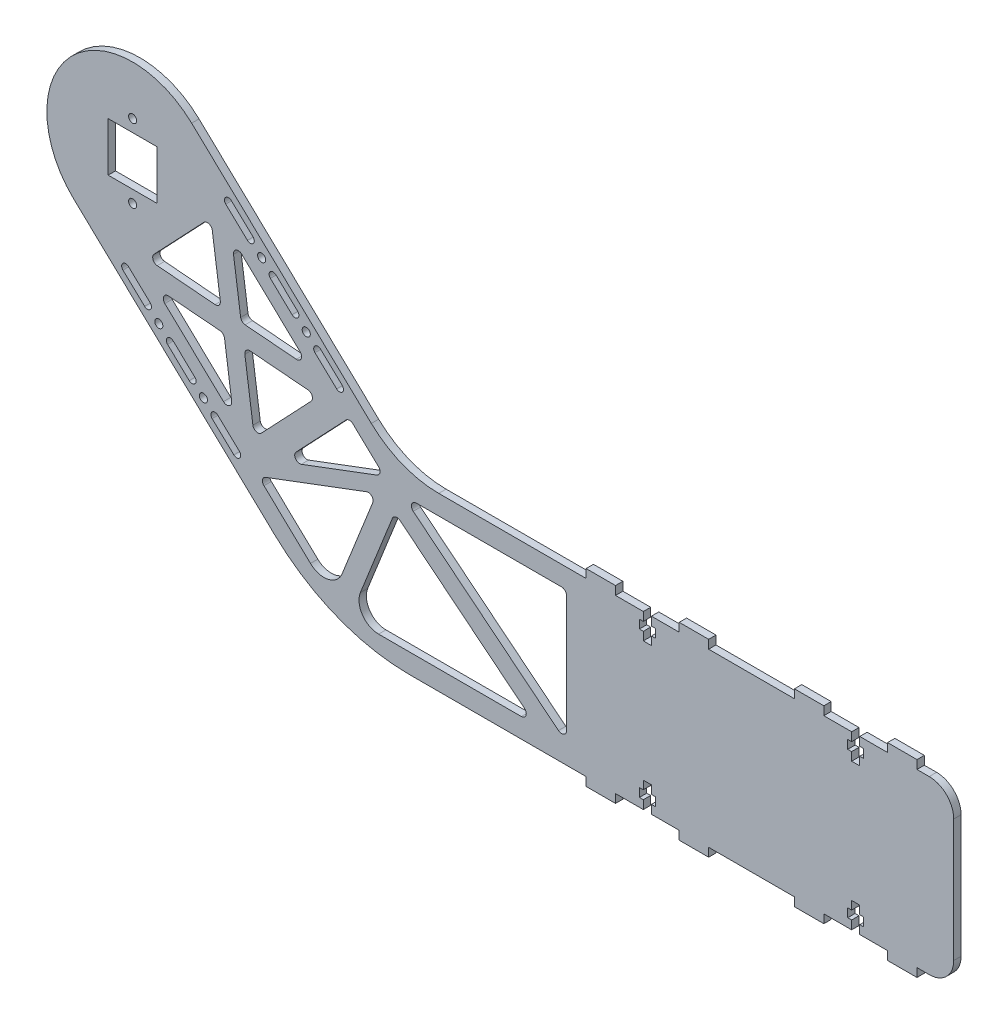
SolidWorks part; units mm, degrees
material "Thornel Mat VMA"
ref_plane "前视基准面" through (0, 0, 0) normal (0, 0, 1) x (1, 0, 0)
ref_plane "上视基准面" through (0, 0, 0) normal (0, 1, 0) x (1, 0, 0)
ref_plane "右视基准面" through (0, 0, 0) normal (1, 0, 0) x (0, 0, -1)
sketch "草图1" plane through (0, 0, 0) normal (0, 0, 1) x (1, 0, 0)
  line L0 (0, 0) -> (95, -90) construction
  line L1 (95, -90) -> (335, -90) construction
  line L2 (-24.0711, -25.4083) -> (81.0535, -125)
  line L3 (81.0535, -125) -> (335, -125)
  line L4 (24.0711, 25.4083) -> (108.9465, -55)
  line L5 (108.9465, -55) -> (335, -55)
  line L6 (335, -55) -> (335, -125)
  circle A1 centre (0, 0) radius 7.65
  circle A2 centre (0, 0) radius 35
  dimension "D6" = 15.3
  dimension "D1" = 240
  dimension "D2" = 335
  dimension "D3" = 90
  dimension "D4" = 35
  dimension "D5" = 35
extrude "凸台-拉伸1" add sketch "草图1" along normal blind 3 contours L2 L3 L6 L5 L4 A1 | A2 A1 region at (167.1612, -80.12, 0) region at (-24.6897, 23.3902, 0)
sketch "草图3" plane through (0, 0, 3) normal (0, 0, 1) x (1, 0, 0)
  line L0 (210, -55) -> (210, -125) construction
  line L1 (293.35, -55) -> (293.35, -58.5)
  line L2 (108.9465, -55) -> (335, -55) construction
  line L3 (293.35, -58.5) -> (291.75, -58.5)
  line L4 (291.75, -58.5) -> (291.75, -62)
  line L5 (81.0535, -125) -> (335, -125) construction
  line L8 (335, -90) -> (97.2271, -90) construction
  line L9 (335, -55) -> (335, -125) construction
  line L12 (39.125, 4.9479) -> (47.9817, -3.4425) construction
  line L13 (40.2598, 6.1458) -> (49.1164, -2.2447)
  line L14 (37.9903, 3.7501) -> (46.8469, -4.6404)
  line L15 (-2.7794, -39.2843) -> (102.3452, -138.876) construction
  line L16 (15.3695, -56.4779) -> (24.2261, -64.8684) construction
  line L17 (16.5042, -55.2801) -> (25.3609, -63.6706)
  line L18 (-20.9762, -22.1416) -> (84.1483, -121.7332)
  line L19 (-20.9762, -22.1416) -> (84.1483, -121.7332) construction
  line L20 (208.35, -55) -> (208.35, -58.5)
  line L21 (20.9762, 22.1416) -> (105.8517, -58.2668)
  line L22 (20.9762, 22.1416) -> (105.8517, -58.2668) construction
  line L25 (208.35, -58.5) -> (206.75, -58.5)
  line L28 (206.75, -58.5) -> (206.75, -62)
  line L31 (206.75, -62) -> (208.35, -62)
  line L34 (14.2347, -57.6758) -> (23.0913, -66.0662)
  line L37 (-2.8274, -39.3352) -> (6.0292, -47.7257) construction
  line L38 (-1.6926, -38.1374) -> (7.164, -46.5278)
  line L39 (-3.9622, -40.533) -> (4.8944, -48.9235)
  line L40 (57.3219, -12.1948) -> (66.1785, -20.5853) construction
  line L41 (58.4567, -10.997) -> (67.3133, -19.3875)
  line L42 (56.1871, -13.3926) -> (65.0437, -21.7831)
  line L43 (15.4175, -56.4271) -> (120.542, -156.0187) construction
  line L44 (33.5663, -73.6207) -> (42.4229, -82.0112) construction
  line L45 (34.7011, -72.4229) -> (43.5577, -80.8134)
  line L46 (32.4315, -74.8185) -> (41.2882, -83.209)
  line L47 (75.5187, -29.3376) -> (84.3754, -37.7281) construction
  line L48 (76.6535, -28.1398) -> (85.5101, -36.5303)
  line L49 (74.384, -30.5354) -> (83.2406, -38.9259)
  line L50 (208.35, -62) -> (208.35, -65.4)
  line L51 (208.35, -65.4) -> (211.65, -65.4)
  line L52 (211.65, -65.4) -> (211.65, -62)
  line L53 (211.65, -62) -> (213.25, -62)
  line L54 (213.25, -62) -> (213.25, -58.5)
  line L55 (213.25, -58.5) -> (211.65, -58.5)
  line L56 (211.65, -58.5) -> (211.65, -55)
  line L57 (208.35, -55) -> (211.65, -55)
  line L58 (208.35, -125) -> (211.65, -125)
  line L59 (211.65, -121.5) -> (211.65, -125)
  line L60 (213.25, -121.5) -> (211.65, -121.5)
  line L61 (213.25, -118) -> (213.25, -121.5)
  line L62 (211.65, -118) -> (213.25, -118)
  line L63 (211.65, -114.6) -> (211.65, -118)
  line L64 (208.35, -114.6) -> (211.65, -114.6)
  line L65 (208.35, -118) -> (208.35, -114.6)
  line L66 (206.75, -118) -> (208.35, -118)
  line L67 (206.75, -121.5) -> (206.75, -118)
  line L68 (208.35, -121.5) -> (206.75, -121.5)
  line L69 (208.35, -125) -> (208.35, -121.5)
  line L70 (291.75, -62) -> (293.35, -62)
  line L71 (293.35, -62) -> (293.35, -65.4)
  line L72 (293.35, -65.4) -> (296.65, -65.4)
  line L73 (296.65, -65.4) -> (296.65, -62)
  line L74 (296.65, -62) -> (298.25, -62)
  line L75 (298.25, -62) -> (298.25, -58.5)
  line L76 (298.25, -58.5) -> (296.65, -58.5)
  line L77 (296.65, -58.5) -> (296.65, -55)
  line L78 (293.35, -55) -> (296.65, -55)
  line L79 (293.35, -125) -> (296.65, -125)
  line L80 (296.65, -121.5) -> (296.65, -125)
  line L81 (298.25, -121.5) -> (296.65, -121.5)
  line L82 (298.25, -118) -> (298.25, -121.5)
  line L83 (296.65, -118) -> (298.25, -118)
  line L84 (296.65, -114.6) -> (296.65, -118)
  line L85 (293.35, -114.6) -> (296.65, -114.6)
  line L86 (293.35, -118) -> (293.35, -114.6)
  line L87 (291.75, -118) -> (293.35, -118)
  line L88 (291.75, -121.5) -> (291.75, -118)
  line L89 (293.35, -121.5) -> (291.75, -121.5)
  line L90 (293.35, -125) -> (293.35, -121.5)
  line L91 (295, -55) -> (295, -125) construction
  arc A23 (-1.6926, -38.1374) -> (-3.9622, -40.533) centre (-2.8274, -39.3352) ccw
  arc A24 (4.8944, -48.9235) -> (7.164, -46.5278) centre (6.0292, -47.7257) ccw
  circle A25 centre (10.6753, -52.1272) radius 1.65
  arc A26 (40.2598, 6.1458) -> (37.9903, 3.7501) centre (39.125, 4.9479) ccw
  arc A27 (46.8469, -4.6404) -> (49.1164, -2.2447) centre (47.9817, -3.4425) ccw
  circle A28 centre (52.6277, -7.8441) radius 1.65
  circle A29 centre (70.8246, -24.9869) radius 1.65
  circle A30 centre (28.8722, -69.27) radius 1.65
  arc A31 (16.5042, -55.2801) -> (14.2347, -57.6758) centre (15.3695, -56.4779) ccw
  arc A32 (23.0913, -66.0662) -> (25.3609, -63.6706) centre (24.2261, -64.8684) ccw
  arc A33 (58.4567, -10.997) -> (56.1871, -13.3926) centre (57.3219, -12.1948) ccw
  arc A34 (65.0437, -21.7831) -> (67.3133, -19.3875) centre (66.1785, -20.5853) ccw
  arc A37 (34.7011, -72.4229) -> (32.4315, -74.8185) centre (33.5663, -73.6207) ccw
  arc A38 (41.2882, -83.209) -> (43.5577, -80.8134) centre (42.4229, -82.0112) ccw
  arc A39 (76.6535, -28.1398) -> (74.384, -30.5354) centre (75.5187, -29.3376) ccw
  arc A40 (83.2406, -38.9259) -> (85.5101, -36.5303) centre (84.3754, -37.7281) ccw
  circle A41 centre (89.0215, -42.1296) radius 1.65 [skipped]
  circle A42 centre (47.069, -86.4128) radius 1.65 [skipped]
  point P21 (213.9, -120.5)
  point P38 (188.9, -120.5)
  point P68 (43.5533, 0.7527)
  point P81 (1.6009, -43.5304)
  point P93 (61.7502, -16.3901)
  point P102 (19.7978, -60.6732)
  point P113 (79.9471, -33.5328)
  point P122 (37.9946, -77.8159)
  dimension "D8" = 3.5
  dimension "D9" = 3.4
  dimension "D10" = 125
  dimension "D11" = 2
  dimension "D14" = 3.3
  dimension "D16" = 3.3
  dimension "D18" = 6.4
  dimension "D22" = 3.3
  dimension "D23" = 6.4
  dimension "D3" = 3.3
  dimension "D4" = 6.5
  dimension "D5" = 3.5
  dimension "D15" = 12.2
  dimension "D17" = 25
  dimension "D19" = 25
  dimension "D20" = 12.2
  dimension "D21" = 3.3
  dimension "D25" = 12.8001
  dimension "D12" = 40
  dimension "D6" = 4.5
  dimension "D7" = 4.5
  dimension "D24" = 3
fillet "圆角1" radius 10 2 edges at (335, -125, 1.5) (335, -55, 1.5)
extrude "切除-拉伸2" cut sketch "草图3" against normal through all
fillet "圆角2" radius 40 1 edges at (108.9465, -55, 1.5)
fillet "圆角3" radius 80 1 edges at (81.0535, -125, 1.5)
sketch "草图4" plane through (0, 0, 3) normal (0, 0, 1) x (1, 0, 0)
  line L0 (211.65, -55) -> (293.35, -55) construction
  line L1 (223, -55) -> (235, -55)
  line L2 (223, -55) -> (223, -51.5)
  line L3 (223, -51.5) -> (235, -51.5)
  line L4 (235, -55) -> (235, -51.5)
  line L5 (124.8854, -55) -> (208.35, -55) construction
  line L6 (197, -55) -> (185, -55)
  line L7 (197, -55) -> (197, -51.5)
  line L8 (197, -51.5) -> (185, -51.5)
  line L9 (185, -55) -> (185, -51.5)
  line L10 (210, -114.6) -> (210, -65.4) construction
  line L11 (211.65, -114.6) -> (208.35, -114.6) construction
  line L12 (208.35, -65.4) -> (211.65, -65.4) construction
  line L13 (335, -90) -> (145.9271, -90) construction
  line L14 (335, -65) -> (335, -115) construction
  line L15 (185, -125) -> (185, -128.5)
  line L16 (197, -128.5) -> (185, -128.5)
  line L17 (197, -125) -> (197, -128.5)
  line L18 (197, -125) -> (185, -125)
  line L19 (235, -125) -> (235, -128.5)
  line L20 (223, -128.5) -> (235, -128.5)
  line L21 (223, -125) -> (223, -128.5)
  line L22 (223, -125) -> (235, -125)
  line L23 (295, -114.6) -> (295, -65.4) construction
  line L24 (296.65, -114.6) -> (293.35, -114.6) construction
  line L25 (293.35, -65.4) -> (296.65, -65.4) construction
  line L26 (211.65, -55) -> (293.35, -55) construction
  line L27 (270, -55) -> (282, -55)
  line L28 (270, -55) -> (270, -51.5)
  line L29 (270, -51.5) -> (282, -51.5)
  line L30 (282, -55) -> (282, -51.5)
  line L31 (296.65, -55) -> (325, -55) construction
  line L32 (308, -55) -> (320, -55)
  line L33 (308, -55) -> (308, -51.5)
  line L34 (308, -51.5) -> (320, -51.5)
  line L35 (320, -55) -> (320, -51.5)
  line L36 (320, -125) -> (320, -128.5)
  line L37 (308, -128.5) -> (320, -128.5)
  line L38 (308, -125) -> (308, -128.5)
  line L39 (308, -125) -> (320, -125)
  line L40 (282, -125) -> (282, -128.5)
  line L41 (270, -128.5) -> (282, -128.5)
  line L42 (270, -125) -> (270, -128.5)
  line L43 (270, -125) -> (282, -125)
  dimension "D1" = 12
  dimension "D2" = 3.5
  dimension "D3" = 12
  dimension "D4" = 3.5
  dimension "D5" = 50
  dimension "D6" = 12
  dimension "D7" = 50
  dimension "D8" = 3.5
extrude "凸台-拉伸2" add sketch "草图4" against normal blind 3
sketch "草图5" plane through (0, 0, 3) normal (0, 0, 1) x (1, 0, 0)
  line L7 (110.0646, -63) -> (177, -63)
  line L8 (177, -63) -> (177, -117)
  line L20 (31.7127, 4.3939) -> (-9.552, -39.1632) construction
  line L21 (72.9713, -29.3898) -> (34.3605, 7.1888) construction
  line L22 (177, -117) -> (110.0646, -63)
  line L23 (106.9652, -70.7783) -> (164.259, -117)
  line L24 (164.259, -117) -> (88.5471, -117)
  line L25 (88.5471, -117) -> (106.9652, -70.7783)
  line L26 (81.1154, -114.0387) -> (99.6285, -67.5784)
  line L27 (99.6285, -67.5784) -> (51.2674, -85.7616)
  line L28 (51.2674, -85.7616) -> (81.1154, -114.0387)
  line L29 (60.7, -75.805) -> (88.4056, -46.5602)
  line L30 (88.4056, -46.5602) -> (102.6329, -60.0387)
  line L31 (102.6329, -60.0387) -> (60.7, -75.805)
  line L32 (124.8854, -15) -> (87.3026, -109.3172) construction
  line L33 (95.9639, -32.7659) -> (54.6992, -76.3231) construction
  line L34 (85.3551, -40.9292) -> (86.8703, -42.3646) construction
  line L35 (39.4821, -76.9522) -> (47.1875, -84.2521) construction
  line L36 (-0.7082, -39.07) -> (-5.3224, -34.6986) construction
  line L37 (-5.3224, -34.6986) -> (86.8703, -42.3646) construction
  line L38 (86.8703, -42.3646) -> (34.3605, 7.1888) construction
  line L39 (34.3605, 7.1888) -> (47.1875, -84.2521) construction
  line L40 (5.864, -31.615) -> (36.1175, -34.1306)
  line L41 (36.1175, -34.1306) -> (31.9082, -4.1238)
  line L42 (31.9082, -4.1238) -> (5.864, -31.615)
  line L43 (8.9971, -39.9031) -> (37.2568, -42.253)
  line L44 (37.2568, -42.253) -> (41.2078, -70.4185)
  line L45 (41.2078, -70.4185) -> (8.9971, -39.9031)
  line L46 (40.3558, -6.7559) -> (44.2911, -34.8103)
  line L47 (44.2911, -34.8103) -> (72.4393, -37.1509)
  line L48 (72.4393, -37.1509) -> (40.3558, -6.7559)
  line L49 (45.4305, -42.9326) -> (75.684, -45.4483)
  line L50 (75.684, -45.4483) -> (49.6397, -72.9394)
  line L51 (49.6397, -72.9394) -> (45.4305, -42.9326)
  line L52 (43.5577, -80.8134) -> (34.7011, -72.4229) construction
  line L53 (7.164, -46.5278) -> (-1.6926, -38.1374) construction
  line L54 (25.3609, -63.6706) -> (16.5042, -55.2801) construction
  line L57 (74.384, -30.5354) -> (83.2406, -38.9259) construction
  line L58 (37.9903, 3.7501) -> (46.8469, -4.6404) construction
  line L59 (-24.0711, -25.4083) -> (57.9117, -103.0762) construction
  line L60 (112.9313, -125) -> (185, -125) construction
  line L61 (24.0711, 25.4083) -> (97.3757, -44.0381) construction
  line L62 (124.8854, -55) -> (185, -55) construction
  line L63 (185, -51.5) -> (185, -55) construction
  arc A0 (97.3757, -44.0381) -> (124.8854, -55) centre (124.8854, -15) ccw construction
  arc A1 (97.3757, -44.0381) -> (124.8854, -55) centre (124.8854, -15) ccw construction
  arc A2 (97.3757, -44.0381) -> (124.8854, -55) centre (124.8854, -15) ccw
  arc A3 (83.2406, -38.9259) -> (85.5101, -36.5303) centre (84.3754, -37.7281) ccw construction
  arc A4 (40.2598, 6.1458) -> (37.9903, 3.7501) centre (39.125, 4.9479) ccw construction
  dimension "D3" = 6
  dimension "D5" = 6
  dimension "D6" = 8
  dimension "D7" = 6
  dimension "D8" = 8
  dimension "D9" = 8
  dimension "D10" = 8
  dimension "D11" = 6
  dimension "D12" = 6
  dimension "D13" = 5
  dimension "D14" = 5
  dimension "D15" = 8
  dimension "D16" = 8
  dimension "D17" = 4
  dimension "D18" = 8
  dimension "D19" = 8
  dimension "D20" = 8
extrude "切除-拉伸3" cut sketch "草图5" against normal through all contours L25 L24 L23 | L22 L8 L7 | L27 L28 L26 | L31 L30 L29 | L45 L44 L43 | L41 L42 L40 | L47 L48 L46 | L51 L49 L50 region at (154.6882, -81, 3) region at (119.9237, -101.5928, 3) region at (77.3371, -89.1262, 3) region at (83.9128, -60.8013, 3) region at (24.6299, -23.2898, 3) region at (29.1539, -50.8582, 3) region at (52.3621, -26.239, 3)
fillet "圆角4" radius 2 22 edges at (110.0646, -63, 1.5) (177, -63, 1.5) (177, -117, 1.5) (164.259, -117, 1.5) (106.9652, -70.7783, 1.5) (99.6285, -67.5784, 1.5) (51.2674, -85.7616, 1.5) (60.7, -75.805, 1.5) (102.6329, -60.0387, 1.5) (88.4056, -46.5602, 1.5) (8.9971, -39.9031, 1.5) (37.2568, -42.253, 1.5) (41.2078, -70.4185, 1.5) (49.6397, -72.9394, 1.5) (75.684, -45.4483, 1.5) (45.4305, -42.9326, 1.5) (44.2911, -34.8103, 1.5) (72.4393, -37.1509, 1.5) (40.3558, -6.7559, 1.5) (36.1175, -34.1306, 1.5) (5.864, -31.615, 1.5) (31.9082, -4.1238, 1.5)
fillet "圆角5" radius 8 2 edges at (81.1154, -114.0387, 1.5) (88.5471, -117, 1.5)
sketch "草图7" plane through (0, 0, 3) normal (0, 0, 1) x (1, 0, 0)
  line L1 (-10, 10) -> (10, 10)
  line L2 (-10, 10) -> (-10, -10)
  line L3 (-10, -10) -> (10, -10)
  line L4 (10, 10) -> (10, -10)
  line L5 (-10, 10) -> (10, -10) construction
  line L6 (-10, -10) -> (10, 10) construction
  circle A0 centre (0, 15) radius 1.65
  circle A1 centre (0, -15) radius 1.65
  point P0 (0, 0)
  point P10 (0, 0)
  point P11 (0, 0)
  dimension "D5" = 3.3
  dimension "D1" = 20
  dimension "D2" = 20
  dimension "D3" = 5
  dimension "D4" = 5
extrude "切除-拉伸4" cut sketch "草图7" against normal through all
